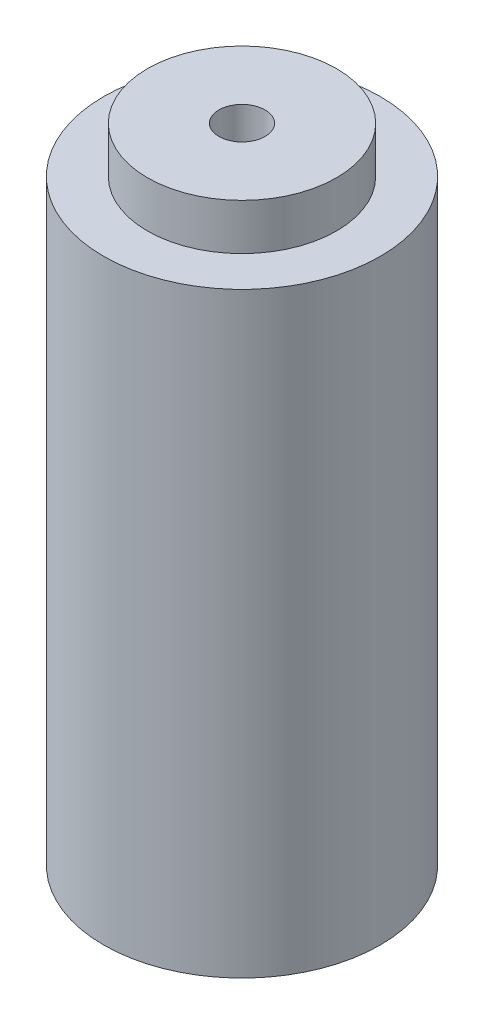
SolidWorks part; units mm, degrees
material "PA Tipo 6"
ref_plane "Plano frontal" through (0, 0, 0) normal (0, 0, 1) x (1, 0, 0)
ref_plane "Plano superior" through (0, 0, 0) normal (0, 1, 0) x (1, 0, 0)
ref_plane "Plano direito" through (0, 0, 0) normal (1, 0, 0) x (0, 0, -1)
sketch "Esboço1" plane through (0, 0, 0) normal (0, 1, 0) x (1, 0, 0)
  circle A0 centre (0, 0) radius 9
  circle A1 centre (0, 0) radius 6.15
  dimension "D1" = 18
  dimension "D2" = 12.3
extrude "Ressalto-extrusão1" add sketch "Esboço1" along normal blind 38.8
extrude "Ressalto-extrusão2" add sketch "Esboço1<2>" along normal blind 41.8 contours A1 region at (0, 0, 0)
sketch "Esboço1<2>" plane through (0, 0, 0) normal (0, 1, 0) x (1, 0, 0) same geometry as "Esboço1"
sketch "Esboço2" plane through (0, 41.8, 0) normal (0, 1, 0) x (1, 0, 0)
  circle A0 centre (0, 0) radius 1.5
  dimension "D1" = 3
extrude "Corte-extrusão1" cut sketch "Esboço2" against normal through all
